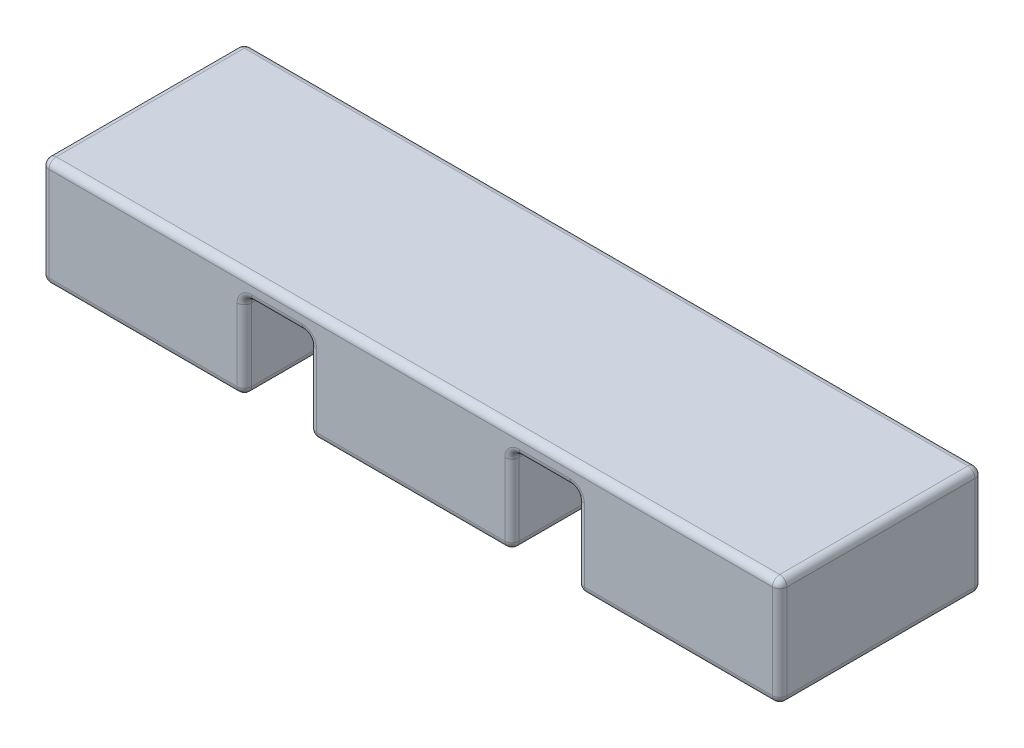
SolidWorks part; units mm, degrees
note: The reader was unsure of these and kept them because the rebuilt part matched: shared geometry of "草图2<3>".
ref_plane "前视基准面" through (0, 0, 0) normal (0, 0, 1) x (1, 0, 0)
ref_plane "上视基准面" through (0, 0, 0) normal (0, 1, 0) x (1, 0, 0)
ref_plane "右视基准面" through (0, 0, 0) normal (1, 0, 0) x (0, 0, -1)
sketch "草图2" plane through (0, 0, 0) normal (0, 1, 0) x (1, 0, 0)
  line L0 (-7, 7) -> (-7, -7) construction
  line L1 (30, 7) -> (44, 7) construction
  line L2 (30, 7) -> (30, -7) construction
  line L3 (30, -7) -> (44, -7) construction
  line L4 (44, 7) -> (44, -7) construction
  line L5 (37, -7) -> (37, 7) construction
  line L6 (30, 0) -> (44, 0) construction
  line L7 (-7, 7) -> (7, 7) construction
  line L8 (7, 7) -> (7, -7) construction
  line L9 (-7, -7) -> (7, -7) construction
  line L10 (-44, 7) -> (-44, -7) construction
  line L11 (-44, 7) -> (-30, 7) construction
  line L12 (-30, 7) -> (-30, -7) construction
  line L13 (-44, -7) -> (-30, -7) construction
  line L14 (30, 7) -> (-7, 7) construction
  line L15 (0, 7) -> (0, -7) construction
  line L16 (-50, 15) -> (50, 15) construction
  line L17 (-50, 15) -> (-50, -15) construction
  line L18 (-50, -15) -> (50, -15) construction
  line L19 (50, 15) -> (50, -15) construction
  line L20 (0, -15) -> (0, 15) construction
  line L21 (-50, 0) -> (50, 0) construction
  line L22 (-45, 10) -> (45, 10) construction
  line L23 (45, 10) -> (45, -10) construction
  line L24 (-45, -10) -> (45, -10) construction
  line L25 (-45, 10) -> (-45, -10) construction
  line L26 (-15, 15) -> (15, 15) construction
  line L27 (-15, 15) -> (-15, -15) construction
  line L28 (-15, -15) -> (15, -15) construction
  line L29 (15, 15) -> (15, -15) construction
  line L30 (0, -15) -> (0, 15) construction
  line L31 (-15, 0) -> (15, 0) construction
  line L32 (-44, 7) -> (-30, -7) construction
  line L33 (-21.5, 15.5) -> (-21.5, -15.5) construction
  line L34 (-52, 15) -> (-22, 15) construction
  line L35 (-52, 15) -> (-52, -15) construction
  line L36 (-52, -15) -> (-22, -15) construction
  line L37 (-22, 15) -> (-22, -15) construction
  line L38 (-37, -15) -> (-37, 15) construction
  line L39 (-52, 0) -> (-22, 0) construction
  line L40 (22, 15) -> (52, 15) construction
  line L41 (22, 15) -> (22, -15) construction
  line L42 (22, -15) -> (52, -15) construction
  line L43 (52, 15) -> (52, -15) construction
  line L44 (37, -15) -> (37, 15) construction
  line L45 (22, 0) -> (52, 0) construction
  line L46 (-52.5, 15.5) -> (52.5, 15.5) construction
  line L47 (-52.5, 15.5) -> (-52.5, -15.5) construction
  line L48 (-52.5, -15.5) -> (52.5, -15.5) construction
  line L49 (52.5, 15.5) -> (52.5, -15.5) construction
  line L50 (-15.5, 15.5) -> (-15.5, -15.5) construction
  line L51 (15.5, 15.5) -> (15.5, -15.5) construction
  line L52 (21.5, 15.5) -> (21.5, -15.5) construction
  line L53 (-45, 10) -> (45, 10) construction
  line L54 (-45, 10) -> (-45, -10) construction
  line L55 (-45, -10) -> (45, -10) construction
  line L56 (45, 10) -> (45, -10) construction
  line L57 (-21.5, -15.5) -> (-15.5, -15.5) construction
  line L58 (15.5, 15.5) -> (21.5, 15.5) construction
  line L59 (15.5, -15.5) -> (21.5, -15.5) construction
  line L64 (-23, 14) -> (-14, 14)
  line L65 (-51, 14) -> (-23, 14)
  line L66 (-51, 14) -> (-51, -14)
  line L67 (-51, -14) -> (-23, -14)
  line L68 (-23, 14) -> (-23, -14)
  line L69 (-37, -14) -> (-37, 14) construction
  line L70 (-51, 0) -> (-23, 0) construction
  line L71 (-14, 14) -> (14, 14)
  line L72 (-14, 14) -> (-14, -14)
  line L73 (-14, -14) -> (14, -14)
  line L74 (14, 14) -> (14, -14)
  line L75 (0, -14) -> (0, 14) construction
  line L76 (-14, 0) -> (14, 0) construction
  line L77 (23, 14) -> (51, 14)
  line L78 (23, 14) -> (23, -14)
  line L79 (23, -14) -> (51, -14)
  line L80 (51, 14) -> (51, -14)
  line L81 (37, -14) -> (37, 14) construction
  line L82 (23, 0) -> (51, 0) construction
  line L83 (14, 14) -> (23, 14)
  line L84 (23, -14) -> (14, -14)
  line L85 (-23, -14) -> (-14, -14)
  circle A0 centre (-45, 10) radius 1.1 construction
  circle A1 centre (-45, -10) radius 1.1 construction
  circle A2 centre (45, 10) radius 1.1 construction
  circle A3 centre (45, -10) radius 1.1 construction
  circle A4 centre (0, -10) radius 1.1 construction
  circle A5 centre (0, 10) radius 1.1 construction
  point P0 (37, 0)
  point P1 (0, 0)
  point P17 (0, 0)
  point P18 (0, 0)
  point P31 (0, 10)
  point P32 (0, -10)
  point P57 (-37, 0)
  point P61 (37, 0)
  point P69 (-37, 0)
  point P88 (0, 0)
  point P93 (37, 0)
  dimension "D6" = 2.2
  dimension "D7" = 2.2
  dimension "D8" = 2.2
  dimension "D9" = 2.2
  dimension "D10" = 2.2
  dimension "D11" = 2.2
  dimension "D1" = 14
  dimension "D2" = 14
  dimension "D3" = 37
  dimension "D4" = 100
  dimension "D5" = 30
  dimension "D12" = 14
  dimension "D13" = 23
  dimension "D14" = 23
  dimension "D15" = 5
  dimension "D16" = 5
  dimension "D17" = 5
  dimension "D18" = 5
  dimension "D19" = 3
  dimension "D20" = 1
  dimension "D21" = 3
  dimension "D22" = 3
  dimension "D23" = 30
  dimension "D24" = 30
  dimension "D25" = 30
  dimension "D26" = 0.5
  dimension "D27" = 0.5
  dimension "D28" = 0.5
  dimension "D29" = 0.5
  dimension "D30" = 0.5
  dimension "D31" = 0.5
  dimension "D32" = 0.5
  dimension "D33" = 0.5
  dimension "D34" = 28
  dimension "D35" = 28
  dimension "D36" = 28
extrude "凸台-拉伸3" add sketch "草图2" against normal blind 12 contours L68 L65 L66 L67 | L74 L71 L72 L73 | L80 L77 L78 L79
extrude "凸台-拉伸4" add sketch "草图2<3>" along normal blind 3 contours L68 L85 L72 L64 | L68 L65 L66 L67 | L74 L71 L72 L73 | L84 L78 L83 L74 | L80 L77 L78 L79
sketch "草图2<3>" plane through (0, 0, 0) normal (0, 1, 0) x (1, 0, 0) same geometry as "草图2"
fillet "圆角1" radius 1 36 edges at (-37, -12, -14) (-51, -12, 0) (0, 3, -14) (51, -4.5, -14) (-18.5, 0, 14) (51, 3, 0) (51, -4.5, 14) (-51, 3, 0) (0, 3, 14) (-18.5, 0, -14) (-37, -12, 14) (18.5, 0, -14) (18.5, 0, 14) (14, 0, 0) (14, -6, -14) (0, -12, 14) (14, -6, 14) (-14, -12, 0) (-14, -6, 14) (-14, -6, -14) (14, -12, 0) (0, -12, -14) (-14, 0, 0) (37, -12, 14) (23, -12, 0) (23, -6, 14) (23, -6, -14) (51, -12, 0) (37, -12, -14) (23, 0, 0) (-23, -12, 0) (-23, 0, 0) (-23, -6, 14) (-51, -4.5, 14) (-51, -4.5, -14) (-23, -6, -14)
